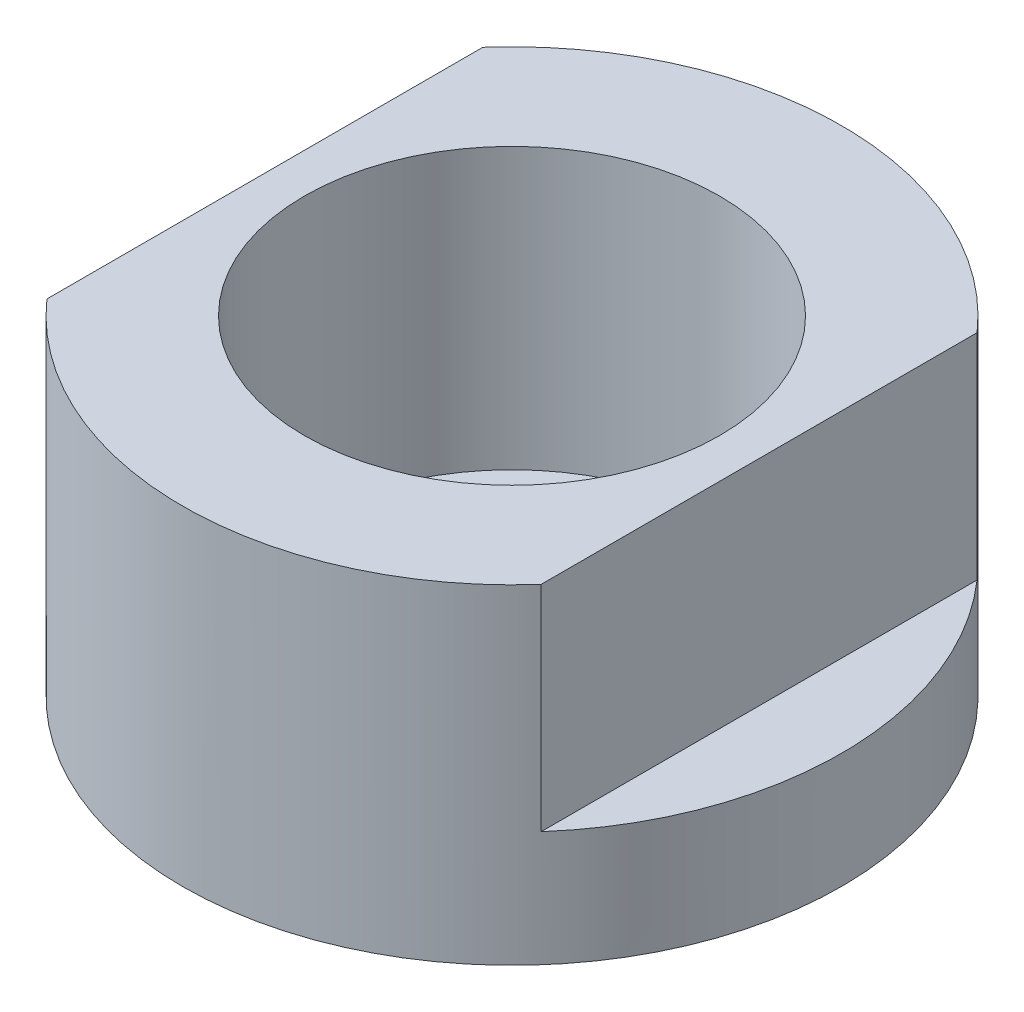
SolidWorks part; units mm, degrees
ref_plane "Front Plane" through (0, 0, 0) normal (0, 0, 1) x (1, 0, 0)
ref_plane "Top Plane" through (0, 0, 0) normal (0, 1, 0) x (1, 0, 0)
ref_plane "Right Plane" through (0, 0, 0) normal (1, 0, 0) x (0, 0, -1)
sketch "Sketch1" plane through (0, 0, 0) normal (0, 1, 0) x (1, 0, 0)
  circle A0 centre (0, 0) radius 25.4
  dimension "D1" = 50.8
extrude "Boss-Extrude1" add sketch "Sketch1" along normal blind 25.4
sketch "Sketch2" plane through (0, 25.4, 0) normal (0, 1, 0) x (1, 0, 0)
  circle A0 centre (0, 0) radius 16
  dimension "D1" = 32
extrude "Cut-Extrude1" cut sketch "Sketch2" against normal offset from surface (21.59 mm away) 3.81 up to face at (0, 0, 25.4)
sketch "Sketch3" plane through (0, 0, 0) normal (0, 0, 1) x (1, 0, 0)
  line L1 (25.4, 25.4) -> (19.05, 25.4)
  line L2 (25.4, 25.4) -> (25.4, 8.89)
  line L3 (25.4, 8.89) -> (19.05, 8.89)
  line L4 (19.05, 25.4) -> (19.05, 8.89)
  line L5 (25.4, 25.4) -> (19.05, 8.89) construction
  line L6 (25.4, 8.89) -> (19.05, 25.4) construction
  line L7 (-25.4, 25.4) -> (-19.05, 25.4)
  line L8 (-25.4, 25.4) -> (-25.4, 8.89)
  line L9 (-25.4, 8.89) -> (-19.05, 8.89)
  line L10 (-19.05, 25.4) -> (-19.05, 8.89)
  line L11 (-25.4, 25.4) -> (-19.05, 8.89) construction
  line L12 (-25.4, 8.89) -> (-19.05, 25.4) construction
  point P4 (22.225, 17.145)
  point P10 (-22.225, 17.145)
  dimension "D1" = 16.51
  dimension "D2" = 38.1
extrude "Cut-Extrude2" cut sketch "Sketch3" against normal up to next and the other way up to next
sketch "Sketch4" plane through (0, 3.81, 0) normal (0, 1, 0) x (1, 0, 0)
  line L0 (0, 0) -> (0, 8.89) construction
  circle A0 centre (0, 8.89) radius 1
  circle A1 centre (7.699, -4.445) radius 1
  circle A2 centre (-7.699, -4.445) radius 1
  point P11 (0, 0)
  dimension "D1" = 2
  dimension "D2" = 8.89
  dimension "D3" = 3
extrude "Cut-Extrude3" cut sketch "Sketch4" against normal up to next
